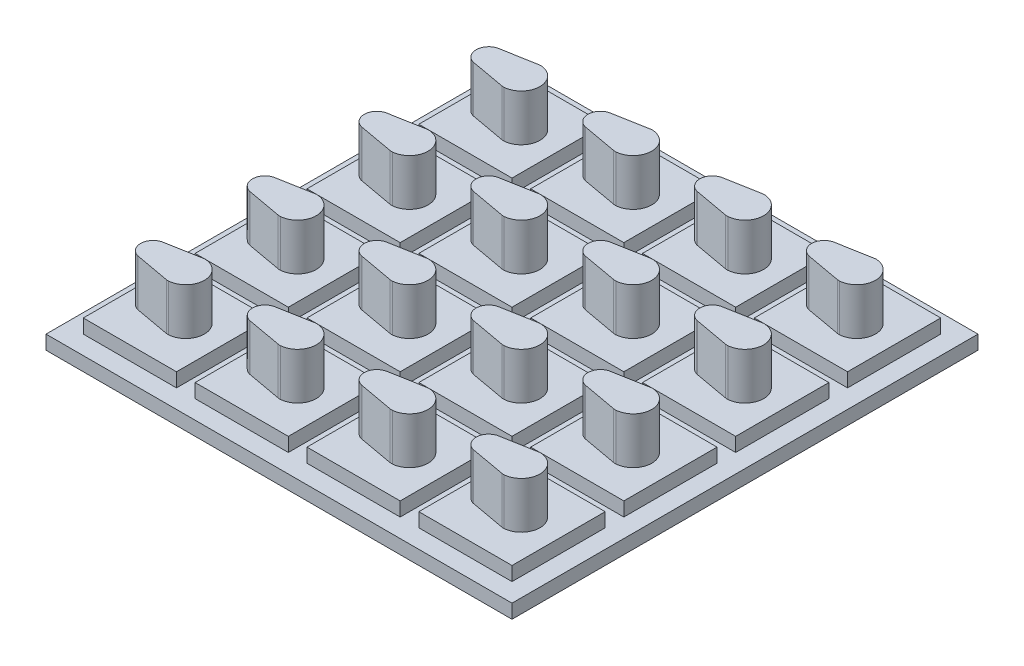
SolidWorks part; units mm, degrees
ref_plane "Front Plane" through (0, 0, 0) normal (0, 0, 1) x (1, 0, 0)
ref_plane "Top Plane" through (0, 0, 0) normal (0, 1, 0) x (1, 0, 0)
ref_plane "Right Plane" through (0, 0, 0) normal (1, 0, 0) x (0, 0, -1)
sketch "Sketch1" plane through (0, 0, 0) normal (0, 1, 0) x (1, 0, 0)
  line L0 (0, 0) -> (-49.3047, 0) construction
  line L9 (-8, 5) -> (-18, 5) construction
  line L10 (-8, 7) -> (-15.8633, 7) construction
  line L11 (-8, 17) -> (-14.8417, 17) construction
  line L12 (-8, -5) -> (-16.8168, -5) construction
  line L13 (-8, 29) -> (-13.8882, 29) construction
  line L14 (-8, 19) -> (-12, 19) construction
  line L15 (-8, -7) -> (-15.1823, -7) construction
  line L16 (-8, -17) -> (-14.6374, -17) construction
  line L18 (-42, 29) -> (-32, 29)
  line L19 (-42, 29) -> (-42, 19)
  line L20 (-42, 19) -> (-32, 19)
  line L21 (-32, 29) -> (-32, 19)
  line L22 (-30, 29) -> (-20, 29)
  line L23 (-30, 29) -> (-30, 19)
  line L24 (-30, 19) -> (-20, 19)
  line L25 (-20, 29) -> (-20, 19)
  line L26 (-18, 29) -> (-8, 29)
  line L27 (-18, 29) -> (-18, 19)
  line L28 (-18, 19) -> (-8, 19)
  line L29 (-8, 29) -> (-8, 19)
  line L30 (-6, 29) -> (4, 29)
  line L31 (-6, 29) -> (-6, 19)
  line L32 (-6, 19) -> (4, 19)
  line L33 (4, 29) -> (4, 19)
  line L34 (-32, 17) -> (-42, 17)
  line L35 (-32, 17) -> (-32, 7)
  line L36 (-32, 7) -> (-42, 7)
  line L37 (-42, 17) -> (-42, 7)
  line L38 (-30, 17) -> (-20, 17)
  line L39 (-30, 17) -> (-30, 7)
  line L40 (-30, 7) -> (-20, 7)
  line L41 (-20, 17) -> (-20, 7)
  line L42 (-18, 7) -> (-8, 7)
  line L43 (-18, 7) -> (-18, 17)
  line L44 (-18, 17) -> (-8, 17)
  line L45 (-8, 7) -> (-8, 17)
  line L46 (-6, 17) -> (4, 17)
  line L47 (-6, 17) -> (-6, 7)
  line L48 (-6, 7) -> (4, 7)
  line L49 (4, 17) -> (4, 7)
  line L50 (-6, 5) -> (4, 5)
  line L51 (-6, 5) -> (-6, -5)
  line L52 (-6, -5) -> (4, -5)
  line L53 (4, 5) -> (4, -5)
  line L54 (-18, -5) -> (-8, -5)
  line L55 (-18, -5) -> (-18, 5)
  line L56 (-18, 5) -> (-8, 5)
  line L57 (-8, -5) -> (-8, 5)
  line L58 (-20, 5) -> (-30, 5)
  line L59 (-20, 5) -> (-20, -5)
  line L60 (-20, -5) -> (-30, -5)
  line L61 (-30, 5) -> (-30, -5)
  line L62 (-32, -5) -> (-42, -5)
  line L63 (-32, -5) -> (-32, 5)
  line L64 (-32, 5) -> (-42, 5)
  line L65 (-42, -5) -> (-42, 5)
  line L66 (-42, -7) -> (-32, -7)
  line L67 (-42, -7) -> (-42, -17)
  line L68 (-42, -17) -> (-32, -17)
  line L69 (-32, -7) -> (-32, -17)
  line L70 (-30, -7) -> (-20, -7)
  line L71 (-30, -7) -> (-30, -17)
  line L72 (-30, -17) -> (-20, -17)
  line L73 (-20, -7) -> (-20, -17)
  line L74 (-18, -7) -> (-8, -7)
  line L75 (-18, -7) -> (-18, -17)
  line L76 (-18, -17) -> (-8, -17)
  line L77 (-8, -7) -> (-8, -17)
  line L78 (-6, -7) -> (4, -7)
  line L79 (-6, -7) -> (-6, -17)
  line L80 (-6, -17) -> (4, -17)
  line L81 (4, -7) -> (4, -17)
  line L82 (-44, 31) -> (6, 31)
  line L83 (-44, 31) -> (-44, -19)
  line L84 (-44, -19) -> (6, -19)
  line L85 (6, 31) -> (6, -19)
  point P1 (-12, 12)
  point P3 (-12, 0)
  point P8 (-24, 0)
  point P10 (0, 24)
  point P11 (-24, 12)
  point P12 (0, 12)
  point P13 (0, -12)
  point P14 (-12, -12)
  point P16 (-24, -12)
  point P19 (-36, 12)
  point P21 (-36, 24)
  point P22 (-24, 24)
  point P23 (-12, 24)
  point P24 (-36, 0)
  point P25 (-36, -12)
  line B0 (-0.1035, 1.9813) -> (-3.7918, 1.315)
  line B1 (-3.7918, -1.315) -> (-0.1035, -1.9813)
  arc B2 (-3.9397, 1.2764) -> (-3.9397, -1.2764) centre (-3.5, 0) ccw
  arc B3 (0.1486, 1.9945) -> (0.1486, -1.9945) centre (0, 0) cw
  arc B4 (-3.9397, 1.2764) -> (-3.7918, 1.315) centre (-3.614, 0.3309) cw
  arc B5 (-3.7918, -1.315) -> (-3.9397, -1.2764) centre (-3.614, -0.3309) cw
  arc B6 (0.1486, 1.9945) -> (-0.1035, 1.9813) centre (0.0743, 0.9972) ccw
  arc B7 (0.1486, -1.9945) -> (-0.1035, -1.9813) centre (0.0743, -0.9972) cw
  line B8 (-12.1035, 1.9813) -> (-15.7918, 1.315)
  line B9 (-15.7918, -1.315) -> (-12.1035, -1.9813)
  arc B10 (-15.9397, 1.2764) -> (-15.9397, -1.2764) centre (-15.5, 0) ccw
  arc B11 (-11.8514, 1.9945) -> (-11.8514, -1.9945) centre (-12, 0) cw
  arc B12 (-15.9397, 1.2764) -> (-15.7918, 1.315) centre (-15.614, 0.3309) cw
  arc B13 (-15.7918, -1.315) -> (-15.9397, -1.2764) centre (-15.614, -0.3309) cw
  arc B14 (-11.8514, 1.9945) -> (-12.1035, 1.9813) centre (-11.9257, 0.9972) ccw
  arc B15 (-11.8514, -1.9945) -> (-12.1035, -1.9813) centre (-11.9257, -0.9972) cw
  line B16 (-24.1035, 1.9813) -> (-27.7918, 1.315)
  line B17 (-27.7918, -1.315) -> (-24.1035, -1.9813)
  arc B18 (-27.9397, 1.2764) -> (-27.9397, -1.2764) centre (-27.5, 0) ccw
  arc B19 (-23.8514, 1.9945) -> (-23.8514, -1.9945) centre (-24, 0) cw
  arc B20 (-27.9397, 1.2764) -> (-27.7918, 1.315) centre (-27.614, 0.3309) cw
  arc B21 (-27.7918, -1.315) -> (-27.9397, -1.2764) centre (-27.614, -0.3309) cw
  arc B22 (-23.8514, 1.9945) -> (-24.1035, 1.9813) centre (-23.9257, 0.9972) ccw
  arc B23 (-23.8514, -1.9945) -> (-24.1035, -1.9813) centre (-23.9257, -0.9972) cw
  line B24 (-0.1035, 13.9813) -> (-3.7918, 13.315)
  line B25 (-3.7918, 10.685) -> (-0.1035, 10.0187)
  arc B26 (-3.9397, 13.2764) -> (-3.9397, 10.7236) centre (-3.5, 12) ccw
  arc B27 (0.1486, 13.9945) -> (0.1486, 10.0055) centre (0, 12) cw
  arc B28 (-3.9397, 13.2764) -> (-3.7918, 13.315) centre (-3.614, 12.3309) cw
  arc B29 (-3.7918, 10.685) -> (-3.9397, 10.7236) centre (-3.614, 11.6691) cw
  arc B30 (0.1486, 13.9945) -> (-0.1035, 13.9813) centre (0.0743, 12.9972) ccw
  arc B31 (0.1486, 10.0055) -> (-0.1035, 10.0187) centre (0.0743, 11.0028) cw
  line B32 (-12.1035, 13.9813) -> (-15.7918, 13.315)
  line B33 (-15.7918, 10.685) -> (-12.1035, 10.0187)
  arc B34 (-15.9397, 13.2764) -> (-15.9397, 10.7236) centre (-15.5, 12) ccw
  arc B35 (-11.8514, 13.9945) -> (-11.8514, 10.0055) centre (-12, 12) cw
  arc B36 (-15.9397, 13.2764) -> (-15.7918, 13.315) centre (-15.614, 12.3309) cw
  arc B37 (-15.7918, 10.685) -> (-15.9397, 10.7236) centre (-15.614, 11.6691) cw
  arc B38 (-11.8514, 13.9945) -> (-12.1035, 13.9813) centre (-11.9257, 12.9972) ccw
  arc B39 (-11.8514, 10.0055) -> (-12.1035, 10.0187) centre (-11.9257, 11.0028) cw
  line B40 (-24.1035, 13.9813) -> (-27.7918, 13.315)
  line B41 (-27.7918, 10.685) -> (-24.1035, 10.0187)
  arc B42 (-27.9397, 13.2764) -> (-27.9397, 10.7236) centre (-27.5, 12) ccw
  arc B43 (-23.8514, 13.9945) -> (-23.8514, 10.0055) centre (-24, 12) cw
  arc B44 (-27.9397, 13.2764) -> (-27.7918, 13.315) centre (-27.614, 12.3309) cw
  arc B45 (-27.7918, 10.685) -> (-27.9397, 10.7236) centre (-27.614, 11.6691) cw
  arc B46 (-23.8514, 13.9945) -> (-24.1035, 13.9813) centre (-23.9257, 12.9972) ccw
  arc B47 (-23.8514, 10.0055) -> (-24.1035, 10.0187) centre (-23.9257, 11.0028) cw
  line B48 (-12.1035, -10.0187) -> (-15.7918, -10.685)
  line B49 (-15.7918, -13.315) -> (-12.1035, -13.9813)
  arc B50 (-15.9397, -10.7236) -> (-15.9397, -13.2764) centre (-15.5, -12) ccw
  arc B51 (-11.8514, -10.0055) -> (-11.8514, -13.9945) centre (-12, -12) cw
  arc B52 (-15.9397, -10.7236) -> (-15.7918, -10.685) centre (-15.614, -11.6691) cw
  arc B53 (-15.7918, -13.315) -> (-15.9397, -13.2764) centre (-15.614, -12.3309) cw
  arc B54 (-11.8514, -10.0055) -> (-12.1035, -10.0187) centre (-11.9257, -11.0028) ccw
  arc B55 (-11.8514, -13.9945) -> (-12.1035, -13.9813) centre (-11.9257, -12.9972) cw
  line B56 (-0.1035, -10.0187) -> (-3.7918, -10.685)
  line B57 (-3.7918, -13.315) -> (-0.1035, -13.9813)
  arc B58 (-3.9397, -10.7236) -> (-3.9397, -13.2764) centre (-3.5, -12) ccw
  arc B59 (0.1486, -10.0055) -> (0.1486, -13.9945) centre (0, -12) cw
  arc B60 (-3.9397, -10.7236) -> (-3.7918, -10.685) centre (-3.614, -11.6691) cw
  arc B61 (-3.7918, -13.315) -> (-3.9397, -13.2764) centre (-3.614, -12.3309) cw
  arc B62 (0.1486, -10.0055) -> (-0.1035, -10.0187) centre (0.0743, -11.0028) ccw
  arc B63 (0.1486, -13.9945) -> (-0.1035, -13.9813) centre (0.0743, -12.9972) cw
  line B64 (-24.1035, -10.0187) -> (-27.7918, -10.685)
  line B65 (-27.7918, -13.315) -> (-24.1035, -13.9813)
  arc B66 (-27.9397, -10.7236) -> (-27.9397, -13.2764) centre (-27.5, -12) ccw
  arc B67 (-23.8514, -10.0055) -> (-23.8514, -13.9945) centre (-24, -12) cw
  arc B68 (-27.9397, -10.7236) -> (-27.7918, -10.685) centre (-27.614, -11.6691) cw
  arc B69 (-27.7918, -13.315) -> (-27.9397, -13.2764) centre (-27.614, -12.3309) cw
  arc B70 (-23.8514, -10.0055) -> (-24.1035, -10.0187) centre (-23.9257, -11.0028) ccw
  arc B71 (-23.8514, -13.9945) -> (-24.1035, -13.9813) centre (-23.9257, -12.9972) cw
  line B72 (-0.1035, 25.9813) -> (-3.7918, 25.315)
  line B73 (-3.7918, 22.685) -> (-0.1035, 22.0187)
  arc B74 (-3.9397, 25.2764) -> (-3.9397, 22.7236) centre (-3.5, 24) ccw
  arc B75 (0.1486, 25.9945) -> (0.1486, 22.0055) centre (0, 24) cw
  arc B76 (-3.9397, 25.2764) -> (-3.7918, 25.315) centre (-3.614, 24.3309) cw
  arc B77 (-3.7918, 22.685) -> (-3.9397, 22.7236) centre (-3.614, 23.6691) cw
  arc B78 (0.1486, 25.9945) -> (-0.1035, 25.9813) centre (0.0743, 24.9972) ccw
  arc B79 (0.1486, 22.0055) -> (-0.1035, 22.0187) centre (0.0743, 23.0028) cw
  line B80 (-12.1035, 25.9813) -> (-15.7918, 25.315)
  line B81 (-15.7918, 22.685) -> (-12.1035, 22.0187)
  arc B82 (-15.9397, 25.2764) -> (-15.9397, 22.7236) centre (-15.5, 24) ccw
  arc B83 (-11.8514, 25.9945) -> (-11.8514, 22.0055) centre (-12, 24) cw
  arc B84 (-15.9397, 25.2764) -> (-15.7918, 25.315) centre (-15.614, 24.3309) cw
  arc B85 (-15.7918, 22.685) -> (-15.9397, 22.7236) centre (-15.614, 23.6691) cw
  arc B86 (-11.8514, 25.9945) -> (-12.1035, 25.9813) centre (-11.9257, 24.9972) ccw
  arc B87 (-11.8514, 22.0055) -> (-12.1035, 22.0187) centre (-11.9257, 23.0028) cw
  line B88 (-24.1035, 25.9813) -> (-27.7918, 25.315)
  line B89 (-27.7918, 22.685) -> (-24.1035, 22.0187)
  arc B90 (-27.9397, 25.2764) -> (-27.9397, 22.7236) centre (-27.5, 24) ccw
  arc B91 (-23.8514, 25.9945) -> (-23.8514, 22.0055) centre (-24, 24) cw
  arc B92 (-27.9397, 25.2764) -> (-27.7918, 25.315) centre (-27.614, 24.3309) cw
  arc B93 (-27.7918, 22.685) -> (-27.9397, 22.7236) centre (-27.614, 23.6691) cw
  arc B94 (-23.8514, 25.9945) -> (-24.1035, 25.9813) centre (-23.9257, 24.9972) ccw
  arc B95 (-23.8514, 22.0055) -> (-24.1035, 22.0187) centre (-23.9257, 23.0028) cw
  line B96 (-36.1035, -10.0187) -> (-39.7918, -10.685)
  line B97 (-39.7918, -13.315) -> (-36.1035, -13.9813)
  arc B98 (-39.9397, -10.7236) -> (-39.9397, -13.2764) centre (-39.5, -12) ccw
  arc B99 (-35.8514, -10.0055) -> (-35.8514, -13.9945) centre (-36, -12) cw
  arc B100 (-39.9397, -10.7236) -> (-39.7918, -10.685) centre (-39.614, -11.6691) cw
  arc B101 (-39.7918, -13.315) -> (-39.9397, -13.2764) centre (-39.614, -12.3309) cw
  arc B102 (-35.8514, -10.0055) -> (-36.1035, -10.0187) centre (-35.9257, -11.0028) ccw
  arc B103 (-35.8514, -13.9945) -> (-36.1035, -13.9813) centre (-35.9257, -12.9972) cw
  line B104 (-36.1035, 25.9813) -> (-39.7918, 25.315)
  line B105 (-39.7918, 22.685) -> (-36.1035, 22.0187)
  arc B106 (-39.9397, 25.2764) -> (-39.9397, 22.7236) centre (-39.5, 24) ccw
  arc B107 (-35.8514, 25.9945) -> (-35.8514, 22.0055) centre (-36, 24) cw
  arc B108 (-39.9397, 25.2764) -> (-39.7918, 25.315) centre (-39.614, 24.3309) cw
  arc B109 (-39.7918, 22.685) -> (-39.9397, 22.7236) centre (-39.614, 23.6691) cw
  arc B110 (-35.8514, 25.9945) -> (-36.1035, 25.9813) centre (-35.9257, 24.9972) ccw
  arc B111 (-35.8514, 22.0055) -> (-36.1035, 22.0187) centre (-35.9257, 23.0028) cw
  line B112 (-36.1035, 1.9813) -> (-39.7918, 1.315)
  line B113 (-39.7918, -1.315) -> (-36.1035, -1.9813)
  arc B114 (-39.9397, 1.2764) -> (-39.9397, -1.2764) centre (-39.5, 0) ccw
  arc B115 (-35.8514, 1.9945) -> (-35.8514, -1.9945) centre (-36, 0) cw
  arc B116 (-39.9397, 1.2764) -> (-39.7918, 1.315) centre (-39.614, 0.3309) cw
  arc B117 (-39.7918, -1.315) -> (-39.9397, -1.2764) centre (-39.614, -0.3309) cw
  arc B118 (-35.8514, 1.9945) -> (-36.1035, 1.9813) centre (-35.9257, 0.9972) ccw
  arc B119 (-35.8514, -1.9945) -> (-36.1035, -1.9813) centre (-35.9257, -0.9972) cw
  line B120 (-36.1035, 13.9813) -> (-39.7918, 13.315)
  line B121 (-39.7918, 10.685) -> (-36.1035, 10.0187)
  arc B122 (-39.9397, 13.2764) -> (-39.9397, 10.7236) centre (-39.5, 12) ccw
  arc B123 (-35.8514, 13.9945) -> (-35.8514, 10.0055) centre (-36, 12) cw
  arc B124 (-39.9397, 13.2764) -> (-39.7918, 13.315) centre (-39.614, 12.3309) cw
  arc B125 (-39.7918, 10.685) -> (-39.9397, 10.7236) centre (-39.614, 11.6691) cw
  arc B126 (-35.8514, 13.9945) -> (-36.1035, 13.9813) centre (-35.9257, 12.9972) ccw
  arc B127 (-35.8514, 10.0055) -> (-36.1035, 10.0187) centre (-35.9257, 11.0028) cw
sketch_block_instance "Block1-4"
sketch_block "Block1"
sketch_block_instance "Block1-6"
sketch_block_instance "Block1-7"
sketch_block_instance "Block1-8"
sketch_block_instance "Block1-9"
sketch_block_instance "Block1-10"
sketch_block_instance "Block1-14"
sketch_block_instance "Block1-15"
sketch_block_instance "Block1-16"
sketch_block_instance "Block1-17"
sketch_block_instance "Block1-18"
sketch_block_instance "Block1-19"
sketch_block_instance "Block1-20"
sketch_block_instance "Block1-21"
sketch_block_instance "Block1-22"
sketch_block_instance "Block1-23"
extrude "Boss-Extrude5" add sketch "Sketch1" along normal blind 1.5 contours L25 L22 L23 L24 B91 B95 B89 B93 B90 B92 B88 B94 | B95 B91 B94 B88 B92 B90 B93 B89 | L34 L37 L36 L35 B123 B127 B121 B125 B122 B124 B120 B126 | B127 B123 B126 B120 B124 B122 B125 B121 | B47 B43 B46 B40 B44 B42 B45 B41 | L41 L38 L39 L40 B43 B47 B41 B45 B42 B44 B40 B46 | B23 B19 B22 B16 B20 B18 B21 B17 | L58 L61 L60 L59 B19 B23 B17 B21 B18 B20 B16 B22 | B119 B115 B118 B112 B116 B114 B117 B113 | L65 L62 L63 L64 B115 B119 B113 B117 B114 B116 B112 B118 | L69 L66 L67 L68 B99 B103 B97 B101 B98 B100 B96 B102 | B103 B99 B102 B96 B100 B98 B101 B97 | B71 B67 B70 B64 B68 B66 B69 B65 | L73 L70 L71 L72 B67 B71 B65 B69 B66 B68 B64 B70 | B55 B51 B54 B48 B52 B50 B53 B49 | L77 L74 L75 L76 B51 B55 B49 B53 B50 B52 B48 B54 | B63 B59 B62 B56 B60 B58 B61 B57 | L81 L78 L79 L80 B59 B63 B57 B61 B58 B60 B56 B62 | L54 L57 L56 L55 B11 B15 B9 B13 B10 B12 B8 B14 | B15 B11 B14 B8 B12 B10 B13 B9 | B7 B3 B6 B0 B4 B2 B5 B1 | L53 L50 L51 L52 B3 B7 B1 B5 B2 B4 B0 B6 | B31 B27 B30 B24 B28 B26 B29 B25 | L49 L46 L47 L48 B27 B31 B25 B29 B26 B28 B24 B30 | B39 B35 B38 B32 B36 B34 B37 B33 | L42 L45 L44 L43 B35 B39 B33 B37 B34 B36 B32 B38 | B87 B83 B86 B80 B84 B82 B85 B81 | L29 L26 L27 L28 B83 B87 B81 B85 B82 B84 B80 B86 | B79 B75 B78 B72 B76 B74 B77 B73 | L33 L30 L31 L32 B75 B79 B73 B77 B74 B76 B72 B78 | L18 L21 L20 L19 region at (-25, 0, -28.8586) region at (-13, 0, -28.8586) region at (-1, 0, -28.8586) region at (-32.1414, 0, -12) region at (-25, 0, -16.8586) region at (-17.8586, 0, -12) region at (-1, 0, -16.8586) region at (-1, 0, -4.8586) region at (-17.8586, 0, 0) region at (-20.1414, 0, 0) region at (-37, 0, 4.8586) region at (-37, 0, 7.1414) region at (-25, 0, 7.1414) region at (-13, 0, 7.1414) region at (-1, 0, 7.1414) region at (-1.2261, 0, 0) region at (-13.2261, 0, 0) region at (-25.2261, 0, 0) region at (-1.2261, 0, -12) region at (-13.2261, 0, -12) region at (-25.2261, 0, -12) region at (-13.2261, 0, 12) region at (-1.2261, 0, 12) region at (-25.2261, 0, 12) region at (-1.2261, 0, -24) region at (-13.2261, 0, -24) region at (-25.2261, 0, -24) region at (-37.2261, 0, 12) region at (-37.2261, 0, 0) region at (-37.2261, 0, -12)
extrude "Boss-Extrude6" add sketch "Sketch1<13>" along normal blind 6.5 contours B111 B107 B110 B104 B108 B106 B109 B105 | B95 B91 B94 B88 B92 B90 B93 B89 | B87 B83 B86 B80 B84 B82 B85 B81 | B79 B75 B78 B72 B76 B74 B77 B73 | B31 B27 B30 B24 B28 B26 B29 B25 | B39 B35 B38 B32 B36 B34 B37 B33 | B47 B43 B46 B40 B44 B42 B45 B41 | B127 B123 B126 B120 B124 B122 B125 B121 | B119 B115 B118 B112 B116 B114 B117 B113 | B23 B19 B22 B16 B20 B18 B21 B17 | B15 B11 B14 B8 B12 B10 B13 B9 | B7 B3 B6 B0 B4 B2 B5 B1 | B63 B59 B62 B56 B60 B58 B61 B57 | B55 B51 B54 B48 B52 B50 B53 B49 | B71 B67 B70 B64 B68 B66 B69 B65 | B103 B99 B102 B96 B100 B98 B101 B97 region at (-1.2261, 0, 0) region at (-13.2261, 0, 0) region at (-25.2261, 0, 0) region at (-1.2261, 0, -12) region at (-13.2261, 0, -12) region at (-25.2261, 0, -12) region at (-13.2261, 0, 12) region at (-1.2261, 0, 12) region at (-25.2261, 0, 12) region at (-1.2261, 0, -24) region at (-13.2261, 0, -24) region at (-25.2261, 0, -24) region at (-37.2261, 0, 12) region at (-37.2261, 0, -24) region at (-37.2261, 0, 0) region at (-37.2261, 0, -12)
sketch "Sketch1<13>" plane through (0, 0, 0) normal (0, 1, 0) x (1, 0, 0) same geometry as "Sketch1"
extrude "Boss-Extrude7" add sketch "Sketch1<15>" against normal blind 1.5 contours L85 L82 L83 L84 L74 L77 L76 L75 L66 L69 L68 L67 L50 L53 L52 L51 L38 L41 L40 L39 L37 L34 L35 L36 L26 L29 L28 L27 L18 L21 L20 L19 L22 L25 L24 L23 L30 L33 L32 L31 L45 | B111 B107 B110 B104 B108 B106 B109 B105 | L21 L18 L19 L20 B107 B111 B105 B109 B106 B108 B104 B110 | L41 L38 L39 L40 B43 B47 B41 B45 B42 B44 B40 B46 | L25 L22 L23 L24 B91 B95 B89 B93 B90 B92 B88 B94 | L29 L26 L27 L28 B83 B87 B81 B85 B82 B84 B80 B86 | L33 L30 L31 L32 B75 B79 B73 B77 B74 B76 B72 B78 | L49 L46 L47 L48 B27 B31 B25 B29 B26 B28 B24 B30 | L53 L50 L51 L52 B3 B7 B1 B5 B2 B4 B0 B6 | L81 L78 L79 L80 B59 B63 B57 B61 B58 B60 B56 B62 | L77 L74 L75 L76 B51 B55 B49 B53 B50 B52 B48 B54 | L73 L70 L71 L72 B67 B71 B65 B69 B66 B68 B64 B70 | L69 L66 L67 L68 B99 B103 B97 B101 B98 B100 B96 B102 | B71 B67 B70 B64 B68 B66 B69 B65 | B55 B51 B54 B48 B52 B50 B53 B49 | B47 B43 B46 B40 B44 B42 B45 B41 | L58 L61 L60 L59 B19 B23 B17 B21 B18 B20 B16 B22 | B23 B19 B22 B16 B20 B18 B21 B17 | L65 L62 L63 L64 B115 B119 B113 B117 B114 B116 B112 B118 | B119 B115 B118 B112 B116 B114 B117 B113 | B79 B75 B78 B72 B76 B74 B77 B73 | B31 B27 B30 B24 B28 B26 B29 B25 | B63 B59 B62 B56 B60 B58 B61 B57 | B7 B3 B6 B0 B4 B2 B5 B1 | B87 B83 B86 B80 B84 B82 B85 B81 | B95 B91 B94 B88 B92 B90 B93 B89 | B103 B99 B102 B96 B100 B98 B101 B97 | L54 L57 L56 L55 B11 B15 B9 B13 B10 B12 B8 B14 | B15 B11 B14 B8 B12 B10 B13 B9 | L42 L45 L44 L43 B35 B39 B33 B37 B34 B36 B32 B38 | B39 B35 B38 B32 B36 B34 B37 B33 | L34 L37 L36 L35 B123 B127 B121 B125 B122 B124 B120 B126 | B127 B123 B126 B120 B124 B122 B125 B121 region at (-37, 0, -28.8586) region at (-25, 0, -28.8586) region at (-13, 0, -28.8586) region at (-1, 0, -28.8586) region at (-32.1414, 0, -12) region at (-25, 0, -16.8586) region at (-17.8586, 0, -12) region at (-1, 0, -16.8586) region at (-1, 0, -4.8586) region at (-17.8586, 0, 0) region at (-20.1414, 0, 0) region at (-37, 0, 4.8586) region at (-37, 0, 7.1414) region at (-25, 0, 7.1414) region at (-13, 0, 7.1414) region at (-1, 0, 7.1414) region at (-19, 0, -6) region at (-1.2261, 0, 0) region at (-13.2261, 0, 0) region at (-25.2261, 0, 0) region at (-1.2261, 0, -12) region at (-13.2261, 0, -12) region at (-25.2261, 0, -12) region at (-13.2261, 0, 12) region at (-1.2261, 0, 12) region at (-25.2261, 0, 12) region at (-1.2261, 0, -24) region at (-13.2261, 0, -24) region at (-25.2261, 0, -24) region at (-37.2261, 0, 12) region at (-37.2261, 0, -24) region at (-37.2261, 0, 0) region at (-37.2261, 0, -12)
sketch "Sketch1<15>" plane through (0, 0, 0) normal (0, 1, 0) x (1, 0, 0) same geometry as "Sketch1"
